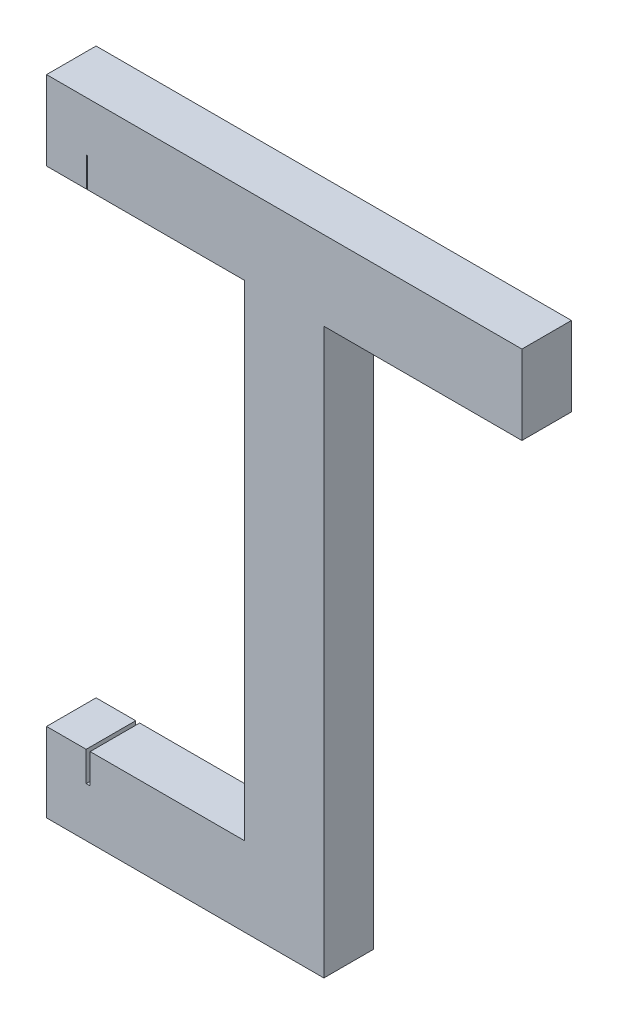
SolidWorks part; units mm, degrees
ref_plane "Front Plane" through (0, 0, 0) normal (0, 0, 1) x (1, 0, 0)
ref_plane "Top Plane" through (0, 0, 0) normal (0, 1, 0) x (1, 0, 0)
ref_plane "Right Plane" through (0, 0, 0) normal (1, 0, 0) x (0, 0, -1)
sketch "Sketch1" plane through (0, 0, 0) normal (0, 0, 1) x (1, 0, 0)
  line L1 (0, 65) -> (-28, 65)
  line L2 (-28, 65) -> (-28, 57)
  line L3 (-28, 57) -> (-8, 57)
  line L4 (-8, 57) -> (-8, 8)
  line L5 (-8, 8) -> (-28, 8)
  line L6 (-28, 8) -> (-28, 0)
  line L7 (-28, 0) -> (0, 0)
  line L11 (0, 0) -> (0, 57)
  line L12 (0, 57) -> (20, 57)
  line L13 (20, 57) -> (20, 65)
  line L14 (20, 65) -> (0, 65)
  dimension "D3" = 8
  dimension "D4" = 20
  dimension "D5" = 20
  dimension "D6" = 65
  dimension "D1" = 20
  dimension "D2" = 8
  dimension "D7" = 8
  dimension "D8" = 20
extrude "Boss-Extrude1" add sketch "Sketch1" along normal blind 5
sketch "Sketch2" plane through (0, 8, 0) normal (0, 1, 0) x (1, 0, 0)
  line L0 (0, 0) -> (-23.8, 0) construction
  line L1 (-8, 0) -> (-28, 0) construction
  line L2 (-23.8, 0) -> (-23.8, -5) construction
  line L3 (-8, -5) -> (-28, -5) construction
  line L5 (-24, -5) -> (-23.6, -5)
  line L6 (-24, -5) -> (-24, 0)
  line L7 (-24, 0) -> (-23.6, 0)
  line L8 (-23.6, -5) -> (-23.6, 0)
  line L9 (-24, -5) -> (-23.6, 0) construction
  line L10 (-24, 0) -> (-23.6, -5) construction
  point P5 (-23.8, -2.5)
  dimension "D1" = 23.8
  dimension "D2" = 0.4
extrude "Cut-Extrude1" cut sketch "Sketch2" against normal blind 3
sketch "Sketch3" plane through (0, 57, 0) normal (0, -1, 0) x (1, 0, 0)
  line L0 (-23.95, 2.5) -> (0, 2.5) construction
  line L3 (-23.95, 5) -> (-23.85, 5)
  line L4 (-23.95, 5) -> (-23.95, 0)
  line L5 (-23.95, 0) -> (-23.85, 0)
  line L6 (-23.85, 5) -> (-23.85, 0)
  line L7 (-23.95, 5) -> (-23.85, 0) construction
  line L8 (-23.95, 0) -> (-23.85, 5) construction
  line L9 (0, 5) -> (0, 0) construction
  dimension "D2" = 0.1
  dimension "D1" = 23.95
extrude "Cut-Extrude2" cut sketch "Sketch3" against normal blind 3
equation "\"A.L\"= 0.07m"
equation "\"A.h\"= 0.007m"
equation "\"A.d\"= 0.005m"
equation "\"A.delta\"= 45.0001"
equation "\"A.w\"= 0m"
equation "\"A.v\"= 0.013m"
equation "\"A.s\"= 0.014m"
equation "\"A.t\"= 0.007m"
equation "\"B.L\"= 0.065m"
equation "\"B.h\"= 0.008m"
equation "\"B.s\"= 0.016m"
equation "\"B.t\"= 0.008m"
equation "\"C.h\"= 0.0065m"
equation "\"C.d\"= 0.005m"
equation "\"C.L\"= 0.05m"
equation "\"C.wmax\"= 0.003m"
equation "\"D.L\"= 0.06m"
equation "\"D.h\"= 0.008m"
equation "\"D.s\"= 0.012m"
equation "\"D.t\"= 0.008m"
equation "\"a_h\"= 0.0001m"
equation "\"a_d\"= 0.005m"
equation "\"a_L\"= 0.008m"
equation "\"b_h\"= 0.0004m"
equation "\"b_d\"= 0.005m"
equation "\"b_L\"= 0.007m"
equation "\"c_h\"= 0.0001m"
equation "\"c_d\"= 0.005m"
equation "\"c_L\"= 0.01m"
equation "\"d_h\"= 0.0001m"
equation "\"d_d\"= 0.005m"
equation "\"d_L\"= 0.01m"
equation "\"S.h\"= 0.015m"
equation "\"S.L\"= 0.09275m"
equation "\"D3@Sketch1\"=\"B.t\""
equation "\"D4@Sketch1\"=\"B.s\"+4"
equation "\"D5@Sketch1\"=\"B.s\"+4"
equation "\"D6@Sketch1\"=\"B.L\""
equation "\"D1@Sketch2\"=\"B.h\"+\"B.s\"-\"b_h\"/2"
equation "\"D2@Sketch2\"=\"b_h\""
equation "\"D2@Sketch3\"=\"c_h\""
equation "\"D2@Sketch1\"=\"B.t\""
equation "\"D7@Sketch1\"=\"B.h\""
equation "\"D1@Sketch3\"=\"B.h\"+\"B.s\"-\"c_h\"/2"
